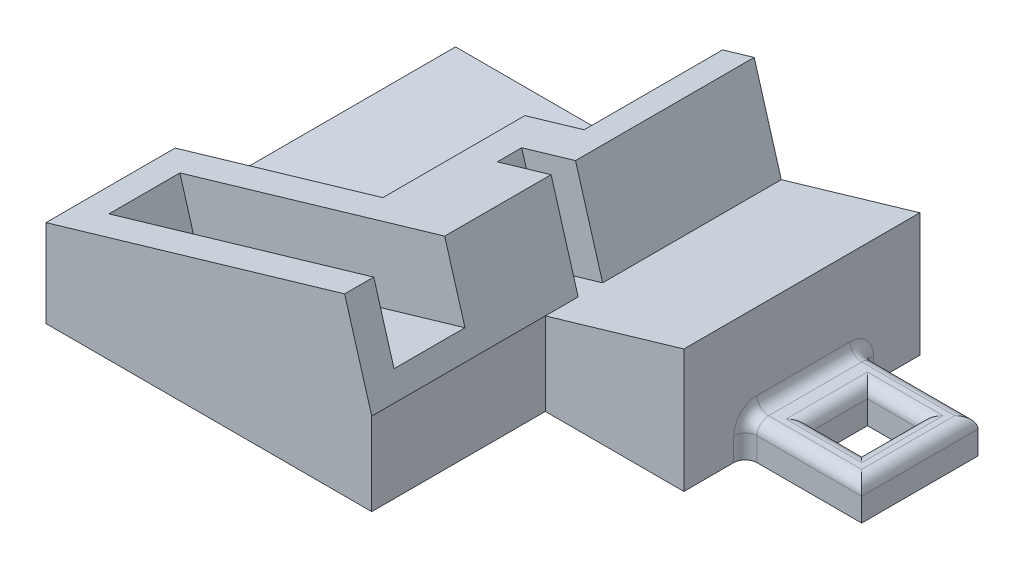
SolidWorks part; units mm, degrees
ref_plane "Front Plane" through (0, 0, 0) normal (0, 0, 1) x (1, 0, 0)
ref_plane "Top Plane" through (0, 0, 0) normal (0, 1, 0) x (1, 0, 0)
ref_plane "Right Plane" through (0, 0, 0) normal (1, 0, 0) x (0, 0, -1)
sketch "Sketch2" plane through (0, 0, 0) normal (0, 1, 0) x (1, 0, 0)
  line L1 (-15.1142, 12.6386) -> (28.8622, 12.6386)
  line L2 (-15.1142, 12.6386) -> (-15.1142, -24.7677)
  line L3 (-15.1142, -24.7677) -> (28.8622, -24.7677)
  line L4 (28.8622, 12.6386) -> (28.8622, -24.7677)
extrude "Boss-Extrude1" add sketch "Sketch2" along normal blind 3
sketch "Sketch3" plane through (0, 0, 0) normal (0, 0, 1) x (1, 0, 0)
  line L0 (3.3227, 11.74) -> (-2.8846, 9.9195)
  line L1 (-2.8846, 9.9195) -> (-11.0544, 7.5234)
  line L2 (-11.0544, 7.5234) -> (-11.0544, 3)
  line L3 (-11.0544, 3) -> (28.8622, 3)
  line L4 (-15.1142, 3) -> (28.8622, 3) construction
  line L5 (28.8622, 3) -> (28.8622, 10.6097)
  line L6 (28.8622, 10.6097) -> (16.9496, 7.1159)
  line L7 (16.9496, 7.1159) -> (14.6215, 15.0538)
  line L8 (14.6215, 15.0538) -> (3.3227, 11.74)
extrude "Boss-Extrude2" add sketch "Sketch3" along normal up to surface and the other way up to surface up to face at (6.874, 1.5, 24.7677) other way up to face at (6.874, 1.5, -12.6386)
sketch "Sketch4" plane through (-2.9073, 9.9128, 0) normal (-0.2814, 0.9596, 0) x (0.9596, 0.2814, 0)
  line L0 (18.2671, 12.6386) -> (18.2671, -24.7677) construction
  line L1 (18.2671, -13.972) -> (-5.4575, -13.972)
  line L2 (18.2671, -13.972) -> (18.2671, -20.072)
  line L3 (18.2671, -20.072) -> (-5.4575, -20.072)
  line L4 (-5.4575, -13.972) -> (-5.4575, -20.072)
extrude "Cut-Extrude1" cut sketch "Sketch4" against normal blind 6.2
sketch "Sketch5" plane through (-0.2956, 0, 0) normal (0, 1, 0) x (1, 0, 0)
  line L0 (17.2451, 12.6386) -> (17.2451, -24.7677) construction
  line L1 (30.6815, -24.7677) -> (17.2451, -24.7677)
  line L2 (30.6815, -24.7677) -> (30.6815, -7.6482)
  line L3 (30.6815, -7.6482) -> (17.2451, -7.6482)
  line L4 (17.2451, -24.7677) -> (17.2451, -7.6482)
extrude "Cut-Extrude2" cut sketch "Sketch5" along normal through all
sketch "Sketch6" plane through (0, 3, 0) normal (0, 1, 0) x (1, 0, 0)
  line L0 (-15.1142, -24.7677) -> (-11.0544, -24.7677) construction
  line L1 (-15.1142, -24.7677) -> (16.9496, -24.7677)
  line L2 (-15.1142, -24.7677) -> (-15.1142, -22.572)
  line L3 (-15.1142, -22.572) -> (16.9496, -22.572)
  line L4 (16.9496, -24.7677) -> (16.9496, -22.572)
  line L5 (16.9496, -7.6482) -> (16.9496, -24.7677) construction
  line L6 (-8.1442, -20.072) -> (14.6215, -20.072) construction
  dimension "D1" = 2.5
extrude "Cut-Extrude3" cut sketch "Sketch6" against normal through all and the other way through all
sketch "Sketch7" plane through (0, 3, 0) normal (0, 1, 0) x (1, 0, 0)
  line L0 (-11.0544, -22.572) -> (-11.0544, 12.6386) construction
  line L1 (-11.0544, 12.6386) -> (6.8051, 12.6386)
  line L2 (-11.0544, 12.6386) -> (-11.0544, -11.472)
  line L3 (-11.0544, -11.472) -> (6.8051, -11.472)
  line L4 (6.8051, 12.6386) -> (6.8051, -11.472)
  line L5 (14.6215, -13.972) -> (-8.1442, -13.972) construction
  dimension "D1" = 2.5
extrude "Cut-Extrude4" cut sketch "Sketch7" along normal through all
sketch "Sketch9" plane through (-2.9073, 9.9128, 0) normal (-0.2814, 0.9596, 0) x (0.9596, 0.2814, 0)
  line L0 (18.546, -2.7231) -> (13.446, -2.7231)
  line L1 (18.296, -2.9731) -> (13.696, -2.9731) construction
  line L2 (18.296, -2.9731) -> (18.296, -4.5731) construction
  line L3 (18.296, -4.5731) -> (13.696, -4.5731) construction
  line L4 (13.696, -2.9731) -> (13.696, -4.5731) construction
  line L5 (13.446, -2.7231) -> (13.446, -4.8231)
  line L6 (18.546, -4.8231) -> (13.446, -4.8231)
  line L7 (18.546, -2.7231) -> (18.546, -4.8231)
  dimension "D1" = 0.25
extrude "Cut-Extrude5" cut sketch "Sketch9" against normal up to surface (8.2722 mm away) up to face at (22.9059, 8.8628, -2.4952)
sketch "Sketch10" plane through (0, 3, 0) normal (0, 1, 0) x (1, 0, 0)
  line L0 (-11.0544, -22.572) -> (14.6215, -22.572) construction
  line L1 (-11.0544, -22.572) -> (-15.1142, -22.572)
  line L2 (-11.0544, -22.572) -> (-11.0544, 12.6386)
  line L3 (-11.0544, 12.6386) -> (-15.1142, 12.6386)
  line L4 (-15.1142, -22.572) -> (-15.1142, 12.6386)
  line L5 (-11.0544, -22.572) -> (-11.0544, -11.472) construction
  line L6 (-15.1142, 12.6386) -> (-15.1142, -22.572) construction
extrude "Cut-Extrude6" cut sketch "Sketch10" against normal through all
sketch "Sketch11" plane through (0, 0, -12.6386) normal (0, 0, -1) x (-1, 0, 0)
  line L0 (-6.8051, 3) -> (-11.9066, 3)
  line L1 (-6.8051, 3) -> (11.0544, 3) construction
  line L2 (-6.8051, 12.7613) -> (-6.8051, 3) construction
  line L3 (-11.9066, 3) -> (-11.9066, 14.2575)
  line L4 (-6.8051, 12.7613) -> (-14.6215, 15.0538) construction
  line L5 (-11.9066, 14.2575) -> (-6.8051, 12.7613)
  line L6 (-6.8051, 12.7613) -> (-6.8051, 3)
extrude "Cut-Extrude7" cut sketch "Sketch11" against normal blind 11.9
sketch "Sketch14" plane through (28.8622, 0, 0) normal (1, 0, 0) x (0, 0, -1)
  line L0 (-7.6482, 0) -> (12.6386, 0) construction
  line L1 (7.6386, 0) -> (-2.3614, 0)
  line L2 (7.6386, 0) -> (7.6386, 3)
  line L3 (7.6386, 3) -> (-2.3614, 3)
  line L4 (-2.3614, 0) -> (-2.3614, 3)
  line L5 (12.6386, 10.6097) -> (12.6386, 0) construction
  dimension "D1" = 10
  dimension "D2" = 3
  dimension "D3" = 5
extrude "Boss-Extrude3" add sketch "Sketch14" along normal blind 10
sketch "Sketch15" plane through (0, 3, 0) normal (0, 1, 0) x (1, 0, 0)
  line L0 (38.8622, 7.6386) -> (38.8622, -2.3614) construction
  line L1 (31.8622, 0.1386) -> (36.3622, 0.1386)
  line L2 (31.8622, 0.1386) -> (31.8622, 5.1386)
  line L3 (31.8622, 5.1386) -> (36.3622, 5.1386)
  line L4 (36.3622, 0.1386) -> (36.3622, 5.1386)
  line L5 (38.8622, -2.3614) -> (28.8622, -2.3614) construction
  line L6 (38.8622, 7.6386) -> (28.8622, 7.6386) construction
  line L7 (28.8622, 7.6386) -> (28.8622, -2.3614) construction
  dimension "D1" = 2.5
  dimension "D2" = 2.5
  dimension "D3" = 2.5
  dimension "D4" = 3
extrude "Cut-Extrude8" cut sketch "Sketch15" against normal through all
fillet "Fillet1" radius 1 10 edges at (33.8622, 3, -7.6386) (38.8622, 3, -2.6386) (33.8622, 3, 2.3614) (28.8622, 3, -2.6386) (36.3622, 3, -2.6386) (34.1122, 3, -5.1386) (31.8622, 3, -2.6386) (34.1122, 3, -0.1386)
